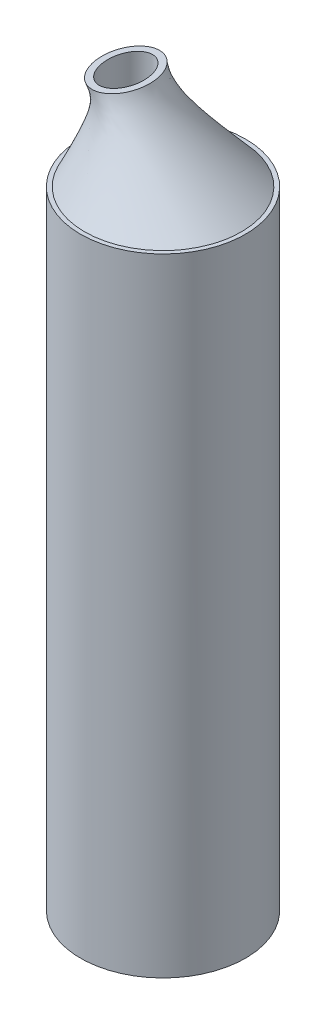
SolidWorks part; units mm, degrees
ref_plane "Front Plane" through (0, 0, 0) normal (0, 0, 1) x (1, 0, 0)
ref_plane "Top Plane" through (0, 0, 0) normal (0, 1, 0) x (1, 0, 0)
ref_plane "Right Plane" through (0, 0, 0) normal (1, 0, 0) x (0, 0, -1)
sketch "Sketch1" plane through (0, 0, 0) normal (0, 1, 0) x (1, 0, 0)
  circle A0 centre (0, 0) radius 20
  circle A1 centre (0, 0) radius 19
  dimension "D1" = 40
  dimension "D2" = 38
extrude "Boss-Extrude1" add sketch "Sketch1" along normal blind 150
ref_plane "Plane1" through (0, 170, 0) normal (0, 1, 0) x (1, 0, 0)
sketch "Sketch3" plane through (0, 170, 0) normal (0, 1, 0) x (1, 0, 0)
  ellipse E0 centre (-9.0201, 0) end of major axis (-9.0201, -8.1917) minor radius 5.7832
sketch "Sketch4" plane through (0, 150, 0) normal (0, 1, 0) x (1, 0, 0)
  circle A1 centre (0, 0) radius 19
loft "Loft1" add profiles "Sketch4", "Sketch3" connector at (-17.692, 150, -6.9277) connector at (-8.8056, 170, -8.1861)
sketch "Sketch7" plane through (0, 170, 0) normal (0, 1, 0) x (1, 0, 0)
  ellipse E0 centre (-9.0201, 0) end of major axis (-9.0201, 6.4736) minor radius 4.3566
extrude "Cut-Extrude3" cut sketch "Sketch7" against normal through all
sketch "Sketch8" plane through (0, 0, 0) normal (0, -1, 0) x (-1, 0, 0)
  circle A0 centre (0, 0) radius 19
sketch "Sketch9" plane through (0, 0, 0) normal (0, -1, 0) x (1, 0, 0)
  circle A0 centre (0, 0) radius 20
extrude "Boss-Extrude3" add sketch "Sketch9" along normal blind 2
sketch "Sketch10" plane through (0, -2, 0) normal (0, -1, 0) x (1, 0, 0)
  circle A0 centre (0, 0) radius 5
  circle A1 centre (-1.2937, 12.4329) radius 5
  circle A2 centre (11.1308, 5.6881) radius 5
  circle A3 centre (9.3178, -8.3324) radius 5
  circle A4 centre (-5.458, -11.2455) radius 5
  circle A5 centre (-12.3111, 2.1651) radius 5
  dimension "D1" = 10
  dimension "D2" = 12.5
  dimension "D5" = 12.5
  dimension "D3" = 12.5
  dimension "D4" = 12.5
  dimension "D6" = 12.5
extrude "Cut-Extrude5" cut sketch "Sketch10" against normal up to next (2 mm away)
ref_plane "Plane2" through (0, 35, 0) normal (0, 1, 0) x (1, 0, 0)
sketch "Sketch11" plane through (0, 35, 0) normal (0, 1, 0) x (1, 0, 0)
  circle A0 centre (0, 0) radius 12.5
  circle A1 centre (0, 0) radius 19
  dimension "D1" = 25
extrude "Boss-Extrude4" add sketch "Sketch11" along normal blind 5
ref_plane "Plane3" through (0, 100, 0) normal (0, 1, 0) x (1, 0, 0)
sketch "Sketch12" plane through (0, 100, 0) normal (0, 1, 0) x (1, 0, 0)
  circle A0 centre (0, 0) radius 19
  circle A1 centre (0, 0) radius 12.5
  dimension "D1" = 25
extrude "Boss-Extrude5" add sketch "Sketch12" along normal blind 5
